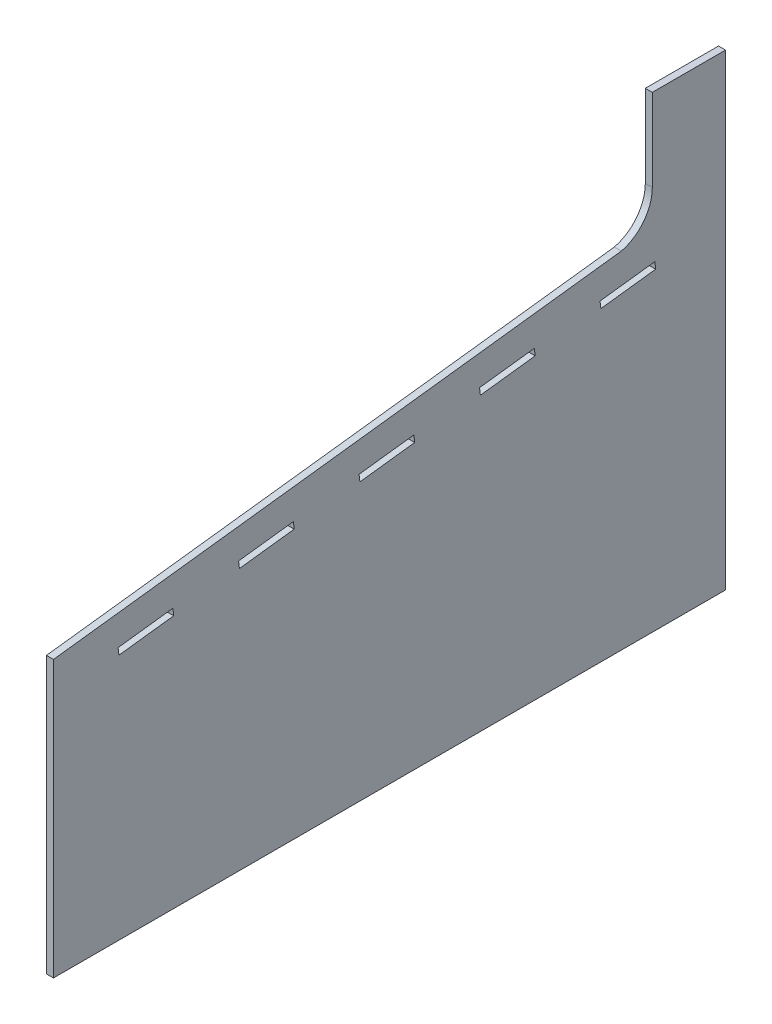
SolidWorks part; units mm, degrees
material "Beech"
ref_plane "Front Plane" through (0, 0, 0) normal (0, 0, 1) x (1, 0, 0)
ref_plane "Top Plane" through (0, 0, 0) normal (0, 1, 0) x (1, 0, 0)
ref_plane "Right Plane" through (0, 0, 0) normal (1, 0, 0) x (0, 0, -1)
sketch "Sketch1" plane through (0, 0, 0) normal (1, 0, 0) x (0, 0, -1)
  line L0 (0, 250) -> (514.5695, 313.1812)
  line L1 (0, 0) -> (609, 0)
  line L2 (0, 0) -> (0, 250)
  line L4 (609, 0) -> (609, 250)
  line L6 (609, 250) -> (609, 423.72)
  line L7 (609, 423.72) -> (542.65, 423.72)
  line L8 (542.65, 349.09) -> (542.65, 423.72)
  line L9 (0, 250) -> (609, 250) construction
  line L10 (514.5695, 313.1812) -> (609, 324.7758) construction
  arc A0 (514.5695, 313.1812) -> (542.65, 349.09) centre (505.65, 349.09) ccw
  dimension "D4" = 37
  dimension "D1" = 609
  dimension "D2" = 250
  dimension "D3" = 66.35
  dimension "D5" = 7
  dimension "D6" = 173.72
  dimension "D7" = 74.63
extrude "Boss-Extrude1" add sketch "Sketch1" along normal blind 6.35
sketch "Sketch2" plane through (6.35, 0, 0) normal (1, 0, 0) x (0, 0, -1)
  line L0 (514.5695, 313.1812) -> (609, 324.7758) construction
  line L1 (609, 0) -> (609, 423.72) construction
  line L2 (514.5695, 313.1812) -> (0, 250) construction
  line L3 (0, 222.7972) -> (609, 297.573) construction
  line L4 (0, 250) -> (0, 0) construction
  line L5 (58.5602, 229.9875) -> (59.3341, 223.6849)
  line L6 (59.3341, 223.6849) -> (108.9614, 229.7783)
  line L7 (108.9614, 229.7783) -> (108.1875, 236.081)
  line L8 (108.1875, 236.081) -> (58.5602, 229.9875)
  line L9 (217.3676, 249.4866) -> (167.7403, 243.3932)
  line L10 (167.7403, 243.3932) -> (168.5142, 237.0905)
  line L11 (168.5142, 237.0905) -> (218.1415, 243.184)
  line L12 (218.1415, 243.184) -> (217.3676, 249.4866)
  line L13 (326.5477, 262.8922) -> (276.9204, 256.7988)
  line L14 (276.9204, 256.7988) -> (277.6942, 250.4961)
  line L15 (277.6942, 250.4961) -> (327.3216, 256.5896)
  line L16 (327.3216, 256.5896) -> (326.5477, 262.8922)
  line L17 (435.7278, 276.2979) -> (386.1005, 270.2044)
  line L18 (386.1005, 270.2044) -> (386.8743, 263.9017)
  line L19 (386.8743, 263.9017) -> (436.5016, 269.9952)
  line L20 (436.5016, 269.9952) -> (435.7278, 276.2979)
  line L21 (544.9078, 289.7035) -> (495.2805, 283.61)
  line L22 (495.2805, 283.61) -> (496.0544, 277.3074)
  line L23 (496.0544, 277.3074) -> (545.6817, 283.4008)
  line L24 (545.6817, 283.4008) -> (544.9078, 289.7035)
  dimension "D1" = 27
  dimension "D2" = 50
  dimension "D3" = 6.35
  dimension "D4" = 59
extrude "Cut-Extrude1" cut sketch "Sketch2" against normal blind 6.35
